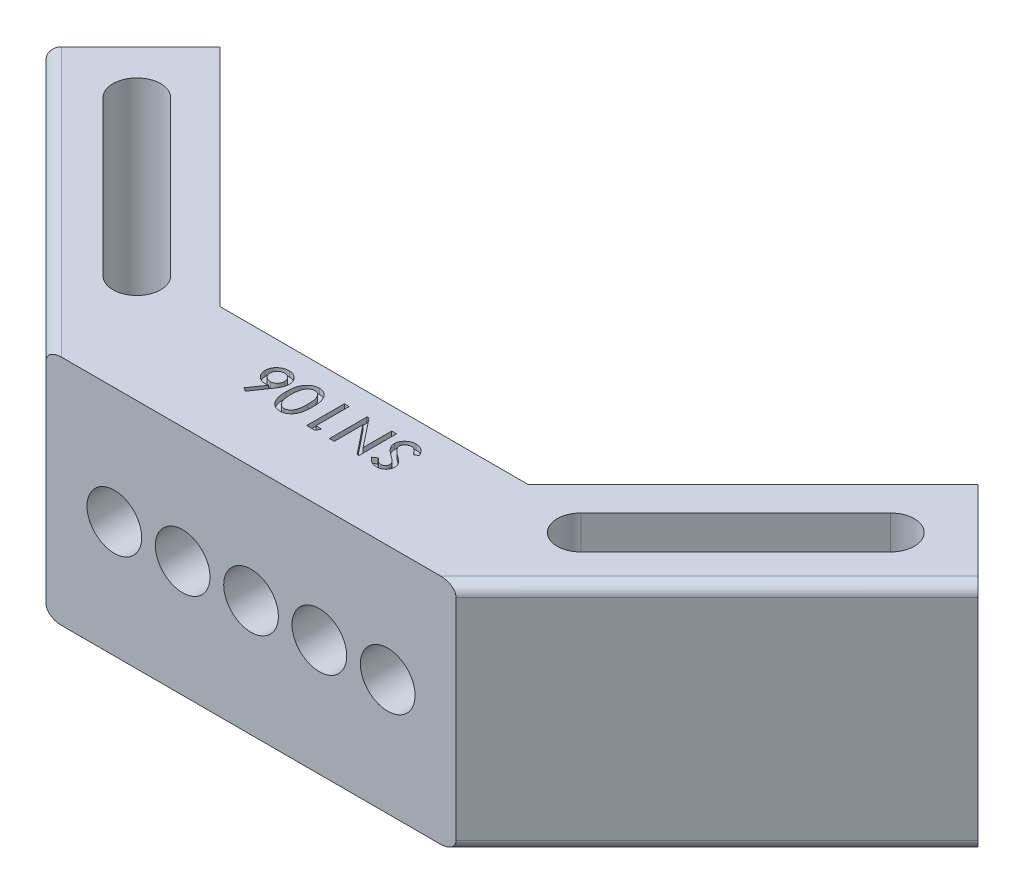
SolidWorks part; units mm, degrees
ref_plane "Front Plane" through (0, 0, 0) normal (0, 0, 1) x (1, 0, 0)
ref_plane "Top Plane" through (0, 0, 0) normal (0, 1, 0) x (1, 0, 0)
ref_plane "Right Plane" through (0, 0, 0) normal (1, 0, 0) x (0, 0, -1)
sketch "Sketch1" plane through (0, 0, 0) normal (0, 1, 0) x (1, 0, 0)
  line L0 (0, 0) -> (0, 17.3832) construction
  line L1 (-19.05, 0) -> (19.05, 0)
  line L2 (19.05, 0) -> (43.2967, 24.2467)
  line L3 (43.2967, 24.2467) -> (35.2145, 32.3289)
  line L4 (35.2145, 32.3289) -> (14.3155, 11.43)
  line L5 (14.3155, 11.43) -> (-14.3155, 11.43)
  line L6 (0, 11.43) -> (0, 0)
  line L7 (-35.2145, 32.3289) -> (-14.3155, 11.43)
  line L8 (-43.2967, 24.2467) -> (-35.2145, 32.3289)
  line L9 (-19.05, 0) -> (-43.2967, 24.2467)
  dimension "D1" = 11.43
  dimension "D2" = 11.43
  dimension "D3" = 38.1
  dimension "D4" = 34.29
  dimension "D5" = 135
extrude "Boss-Extrude1" add sketch "Sketch1" along normal mid plane 21.59 contours L9 L1 L6 L5 L7 L8 | L5 L6 L1 L2 L3 L4 region at (-21.3036, 0, -12.9556) region at (21.3036, 0, -12.9556)
sketch "Sketch2" plane through (0, 0, -11.43) normal (0, 0, -1) x (-1, 0, 0)
  line L0 (0, 0) -> (0, 10.795) construction
  line L1 (-14.3155, 10.795) -> (14.3155, 10.795) construction
  line L2 (0, 0) -> (-12.7, 0) construction
  line L3 (-12.7, 6.35) -> (12.7, 6.35)
  line L4 (-12.7, -6.35) -> (12.7, -6.35)
  circle A0 centre (0, 0) radius 2.54
  circle A1 centre (-12.7, 0) radius 2.54
  circle A2 centre (12.7, 0) radius 2.54
  arc A4 (12.7, -6.35) -> (12.7, 6.35) centre (12.7, 0) ccw
  arc A5 (-12.7, 6.35) -> (-12.7, -6.35) centre (-12.7, 0) ccw
  circle A6 centre (-6.35, 0) radius 2.54
  circle A7 centre (6.35, 0) radius 2.54
  line M3 (14.3155, -10.795) -> (14.3155, 10.795)
  line M5 (-14.3155, 10.795) -> (-14.3155, -10.795)
  dimension "D1" = 5.08
  dimension "D3" = 6.35
  dimension "D2" = 12.7
extrude "Cut-Extrude1" cut sketch "Sketch2" against normal through all both and the other way through all contours A1 M5 | A0 | A2 M3 | A1 M5 | A2 M3 | A6 | A7 region at (14.6918, 0, -11.43) region at (12.4172, 0, -11.43) region at (-12.4172, 0, -11.43) region at (-14.6918, 0, -11.43) region at (0, 0, -11.43) region at (6.35, 0, -11.43) region at (-6.35, 0, -11.43)
sketch "Sketch3" plane through (0, 10.795, 0) normal (0, 1, 0) x (1, 0, 0)
  line L0 (-6.35, 0) -> (-6.35, 11.43)
  line L1 (0, -55) -> (0, 55) construction
  line L2 (-19.05, 0) -> (19.05, 0) construction
  line L3 (6.35, 0) -> (6.35, 11.43)
  point P5 (0, 0)
  dimension "D1" = 6.35
sketch "Sketch4" plane through (0, 0, 0) normal (0, 0, 1) x (1, 0, 0)
  line L0 (-6.35, 10.795) -> (-6.35, -11.1125) construction
  line L1 (0, -55) -> (0, 55) construction
  line L2 (6.35, 10.795) -> (6.35, -11.1125) construction
fillet "Fillet1" radius 1.016 4 edges at (-31.1733, -10.795, -12.1233) (31.1733, -10.795, -12.1233) (-31.1733, 10.795, -12.1233) (31.1733, 10.795, -12.1233)
extrude "Cut-Extrude2" cut sketch "Sketch2<4>" against normal blind 3.81 and the other way through all
sketch "Sketch2<4>" plane through (0, 0, -11.43) normal (0, 0, -1) x (-1, 0, 0) same geometry as "Sketch2"
sketch "Sketch5" plane through (0, 10.795, 0) normal (0, 1, 0) x (1, 0, 0)
  line L0 (-39.076, 28.4674) -> (-10.6086, 0) construction
  line L1 (-17.6132, 0) -> (17.6132, 0) construction
  line L2 (-42.5783, 24.9651) -> (-35.2145, 32.3289) construction
  line L3 (-35.2145, 32.3289) -> (-14.3155, 11.43) construction
  line L4 (-20.6367, 10.0281) -> (-35.0051, 24.3965) construction
  line L5 (-22.2082, 8.4566) -> (-36.5767, 22.825)
  line L6 (-19.0652, 11.5997) -> (-33.4336, 25.9681)
  circle A0 centre (-34.3164, 23.7079) radius 2.2225
  circle A1 centre (-34.3164, 23.7079) radius 2.2225
  arc A3 (-22.2082, 8.4566) -> (-19.0652, 11.5997) centre (-20.6367, 10.0281) ccw
  arc A4 (-33.4336, 25.9681) -> (-36.5767, 22.825) centre (-35.0051, 24.3965) ccw
  point P17 (-27.8209, 17.2123)
  dimension ".2" = 4.445
  dimension "D2" = 5.461
  dimension "D3" = 6.731
  dimension "D4" = 20.32
extrude "Cut-Extrude3" cut sketch "Sketch5" against normal through all contours L6 A0 L5 | A0 | L6 A4 L5 A0 | A3 L6 A4 L5 region at (-26.2423, 10.795, -15.6337) region at (-35.8951, 10.795, -25.2865) region at (-34.3164, 10.795, -23.7079)
mirror "Mirror1" about plane through (0, 0, 0) normal (1, 0, 0) of "Cut-Extrude3"
sketch "Sketch6" plane through (0, -10.795, 0) normal (0, -1, 0) x (1, 0, 0)
  line L0 (42.1804, -9.391) -> (-42.1804, -9.391) construction
  line L1 (-17.6132, 0) -> (17.6132, 0) construction
  line L2 (0, 0) -> (0, -11.43) construction
  line L3 (14.3155, -11.43) -> (-14.3155, -11.43) construction
  text T0 "<b>SN106</b>"
  point P8 (0, -9.391)
extrude "Cut-Extrude4" cut sketch "Sketch6" against normal blind 0.5
sketch "Sketch7" plane through (0, 10.795, 0) normal (0, 1, 0) x (1, 0, 0)
  line L0 (42.1804, 9.391) -> (-42.1804, 9.391) construction
  line L1 (42.1804, 9.391) -> (-42.1804, 9.391) construction
  text T0 "<b>SN106</b>"
extrude "Cut-Extrude5" cut sketch "Sketch7" against normal blind 0.5
